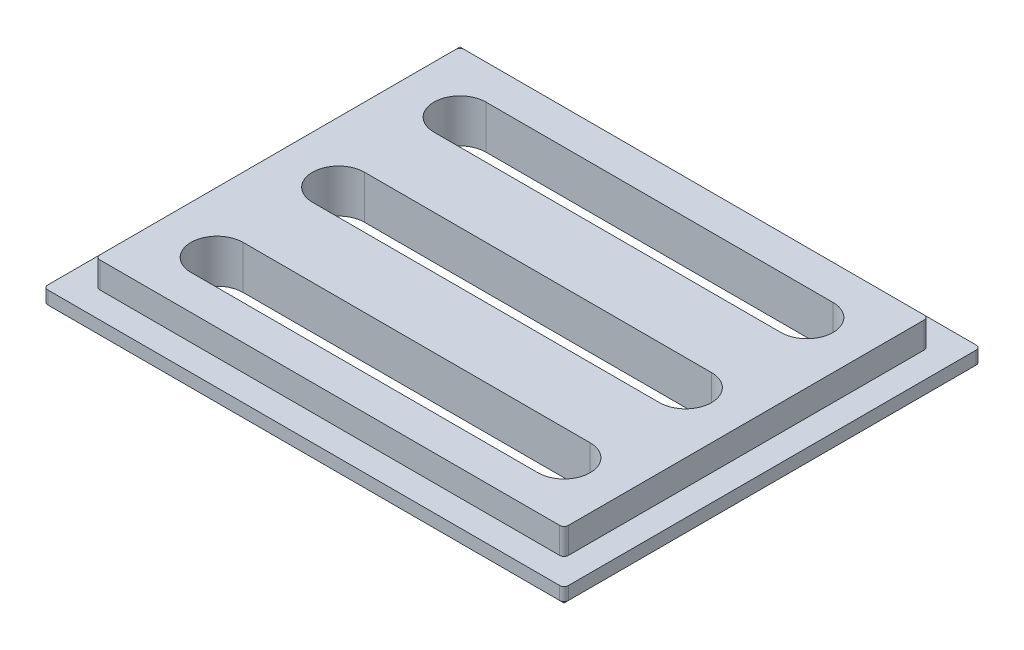
SolidWorks part; units mm, degrees
ref_plane "Front Plane" through (0, 0, 0) normal (0, 0, 1) x (1, 0, 0)
ref_plane "Top Plane" through (0, 0, 0) normal (0, 1, 0) x (1, 0, 0)
ref_plane "Right Plane" through (0, 0, 0) normal (1, 0, 0) x (0, 0, -1)
sketch "Sketch1" plane through (0, 0, 0) normal (0, 1, 0) x (1, 0, 0)
  line L1 (30, -24) -> (-30, -24)
  line L2 (30, -24) -> (30, 24)
  line L3 (30, 24) -> (-30, 24)
  line L4 (-30, -24) -> (-30, 24)
  line L5 (30, -24) -> (-30, 24) construction
  line L6 (30, 24) -> (-30, -24) construction
  point P0 (0, 0)
  dimension "D1" = 48
  dimension "D2" = 60
extrude "Boss-Extrude1" add sketch "Sketch1" along normal blind 2
sketch "Sketch2" plane through (0, 2, 0) normal (0, 1, 0) x (1, 0, 0)
  line L0 (-30, 24) -> (-30, -24) construction
  line L1 (27, -21) -> (-27, -21)
  line L2 (27, -21) -> (27, 21)
  line L3 (27, 21) -> (-27, 21)
  line L4 (-27, -21) -> (-27, 21)
  line L5 (27, -21) -> (-27, 21) construction
  line L6 (27, 21) -> (-27, -21) construction
  line L7 (30, 24) -> (-30, 24) construction
  point P1 (0, 0)
  dimension "D1" = 3
  dimension "D2" = 3
extrude "Boss-Extrude2" add sketch "Sketch2" along normal blind 3
sketch "Sketch4" plane through (0, 5, 0) normal (0, 1, 0) x (1, 0, 0)
  line L0 (-27, 0) -> (27, 0) construction
  line L1 (-27, 21) -> (-27, -21) construction
  line L2 (27, -21) -> (27, 21) construction
  line L5 (0, 21) -> (0, -21) construction
  line L6 (27, 21) -> (-27, 21) construction
  line L7 (-27, -21) -> (27, -21) construction
  line L8 (-20, -3) -> (20, -3)
  line L9 (-20, 11) -> (20, 11)
  line L11 (-20, 17) -> (20, 17)
  line L13 (-20, 11) -> (20, 17) construction
  line L14 (-20, 17) -> (20, 11) construction
  line L15 (-20, 3) -> (20, 3)
  line L16 (-20, -17) -> (20, -17)
  line L17 (-20, -11) -> (20, -11)
  arc A0 (20, 11) -> (20, 17) centre (20, 14) ccw
  arc A1 (-20, 17) -> (-20, 11) centre (-20, 14) ccw
  arc A2 (20, -3) -> (20, 3) centre (20, 0) ccw
  arc A3 (-20, 3) -> (-20, -3) centre (-20, 0) ccw
  arc A4 (20, -17) -> (20, -11) centre (20, -14) ccw
  arc A5 (-20, -11) -> (-20, -17) centre (-20, -14) ccw
  point P6 (0, 0)
  point P7 (0, 0)
  point P8 (41.7366, 11)
  point P9 (0, 17)
  point P16 (0, 14)
  point P24 (-20, 2)
  point P36 (20, -2)
  point P37 (0, 0)
  point P38 (0, 0)
  dimension "D1" = 8
  dimension "D2" = 40
  dimension "D3" = 3
  dimension "8" = 6
extrude "Cut-Extrude1" cut sketch "Sketch4" against normal blind 50
fillet "Fillet1" radius 0.5 7 edges at (-30, 1, 24) (30, 1, 24) (30, 1, -24) (27, 3.5, -21) (-27, 3.5, -21) (27, 3.5, 21) (-27, 3.5, 21)
chamfer "Chamfer1" distance 0.5 angle 45 7 edges at (30, 0, 0) (-0.25, 0, -24) (-30, 0, -0.25) (29.8536, 0, -23.8536) (-29.8536, 0, 23.8536) (29.8536, 0, 23.8536) (0, 0, 24)
